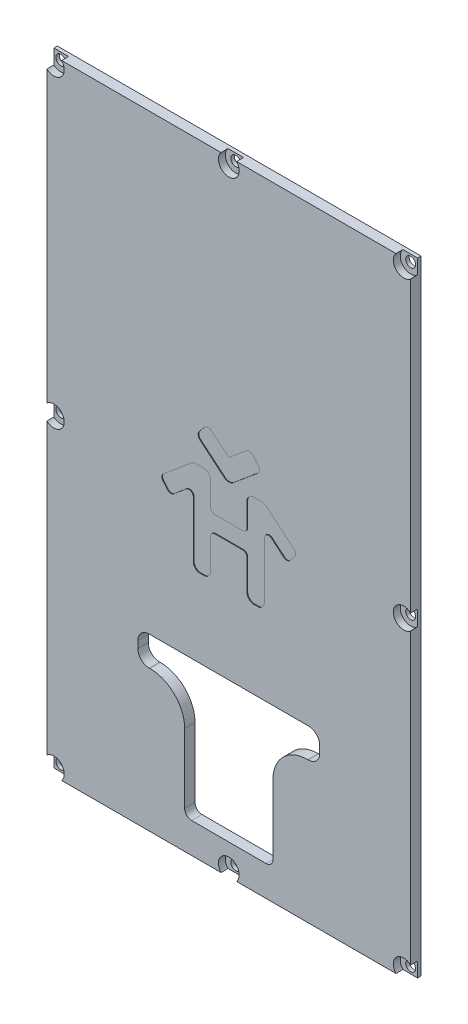
SolidWorks part; units mm, degrees
ref_plane "Спереди" through (0, 0, 0) normal (0, 0, 1) x (1, 0, 0)
ref_plane "Сверху" through (0, 0, 0) normal (0, 1, 0) x (1, 0, 0)
ref_plane "Справа" through (0, 0, 0) normal (1, 0, 0) x (0, 0, -1)
sketch "Эскиз1" plane through (0, 0, 0) normal (0, 0, 1) x (1, 0, 0)
  line L1 (-52.5, -90) -> (52.5, -90)
  line L2 (-52.5, -90) -> (-52.5, 90)
  line L3 (-52.5, 90) -> (52.5, 90)
  line L4 (52.5, -90) -> (52.5, 90)
  line L5 (-52.5, -90) -> (52.5, 90) construction
  line L6 (-52.5, 90) -> (52.5, -90) construction
  point P0 (0, 0)
  dimension "D1" = 105
  dimension "D2" = 180
extrude "Бобышка-Вытянуть1" add sketch "Эскиз1" along normal blind 3
sketch "Эскиз2" plane through (0, 0, 0) normal (0, 0, -1) x (-1, 0, 0)
  line L0 (-26.25, -44) -> (-26.25, -46)
  line L1 (-23, -49.25) -> (-22.75, -49.25)
  line L2 (-12.75, -59.25) -> (-12.75, -79.25)
  line L3 (-10.75, -81.25) -> (10.75, -81.25)
  line L4 (12.75, -79.25) -> (12.75, -59.25)
  line L5 (22.75, -49.25) -> (23, -49.25)
  line L6 (26.25, -46) -> (26.25, -44)
  line L7 (23, -40.75) -> (-23, -40.75)
  line L8 (-52.5, -90) -> (-52.5, 90) construction
  line L9 (52.5, 90) -> (52.5, -90) construction
  line L10 (52.5, -90) -> (-52.5, -90) construction
  arc A0 (22.75, -49.25) -> (12.75, -59.25) centre (22.75, -59.25) ccw
  arc A1 (-12.75, -59.25) -> (-22.75, -49.25) centre (-22.75, -59.25) ccw
  arc A2 (23, -49.25) -> (26.25, -46) centre (23, -46) ccw
  arc A3 (26.25, -44) -> (23, -40.75) centre (23, -44) ccw
  arc A4 (-23, -49.25) -> (-26.25, -46) centre (-23, -46) cw
  arc A5 (-23, -40.75) -> (-26.25, -44) centre (-23, -44) ccw
  arc A6 (12.75, -79.25) -> (10.75, -81.25) centre (10.75, -79.25) cw
  arc A7 (-10.75, -81.25) -> (-12.75, -79.25) centre (-10.75, -79.25) cw
  point P16 (12.75, -49.25)
  point P21 (26.25, -49.25)
  point P24 (26.25, -40.75)
  point P31 (12.75, -81.25)
  point P34 (-12.75, -81.25)
  dimension "D7" = 10
  dimension "D8" = 3.25
  dimension "D9" = 2
  dimension "D1" = 26.25
  dimension "D2" = 26.25
  dimension "D3" = 49.25
  dimension "D4" = 8.5
  dimension "D5" = 25.5
  dimension "D6" = 32
extrude "Вырез-Вытянуть1" cut sketch "Эскиз2" against normal blind 10
sketch "Эскиз3" plane through (0, 0, 3) normal (0, 0, 1) x (1, 0, 0)
  line L0 (-50.5, -940.9285) -> (-50.5, 49059.0715) construction
  line L1 (50.5, -944.6511) -> (50.5, 49055.3489) construction
  line L2 (-1032.3277, 88) -> (48967.6723, 88) construction
  line L3 (-1028.801, -88) -> (48971.199, -88) construction
  line L4 (-52.5, -90) -> (52.5, -90) construction
  line L6 (-52.5, 90) -> (-52.5, -90) construction
  line L7 (52.5, -90) -> (52.5, 90) construction
  line L8 (52.5, 90) -> (-52.5, 90) construction
  line L9 (0, -925) -> (0, 49075) construction
  line L10 (-1052.5, 0) -> (48947.5, 0) construction
  circle A0 centre (-50.5, 88) radius 3
  circle A1 centre (0, 88) radius 3
  circle A2 centre (50.5, 88) radius 3
  circle A3 centre (50.5, 0) radius 3
  circle A4 centre (50.5, -88) radius 3
  circle A5 centre (0, -88) radius 3
  circle A6 centre (-50.5, -88) radius 3
  circle A7 centre (-50.5, 0) radius 3
  point P19 (0, 90)
  point P22 (-52.5, 0)
  dimension "D5" = 6
  dimension "D1" = 2
  dimension "D2" = 2
  dimension "D3" = 2
  dimension "D4" = 2
extrude "Вырез-Вытянуть2" cut sketch "Эскиз3" against normal blind 2
sketch "Эскиз4" plane through (0, 0, 1) normal (0, 0, 1) x (1, 0, 0)
  circle A0 centre (-50.5, 88) radius 1.425
  circle A1 centre (0, 88) radius 1.425
  circle A2 centre (50.5, 88) radius 1.425
  circle A3 centre (50.5, 0) radius 1.425
  circle A4 centre (50.5, -88) radius 1.425
  circle A5 centre (0, -88) radius 1.425
  circle A6 centre (-50.5, -88) radius 1.425
  circle A7 centre (-50.5, 0) radius 1.425
  dimension "D1" = 2.85
extrude "Вырез-Вытянуть3" cut sketch "Эскиз4" against normal blind 2
sketch "Эскиз5" plane through (0, 0, 3) normal (0, 0, 1) x (1, 0, 0)
  line L0 (-10.25, -0.0911) -> (-10.25, -16.2185)
  line L1 (-8.25, -18.2185) -> (-7.25, -18.2185)
  line L2 (-5.25, -16.2185) -> (-5.25, -7.4685)
  line L3 (-4, -6.2185) -> (4, -6.2185)
  line L4 (-9.3401, 8.5815) -> (-7.25, 8.5815)
  line L5 (-5.25, 6.5815) -> (-5.25, -0.1685)
  line L6 (0, -1000.6685) -> (0, 48999.3315) construction
  line L7 (-4, -1.4185) -> (4, -1.4185)
  line L8 (-10.947, 7.9966) -> (-18.868, 1.3501)
  line L9 (-19.0221, -0.4109) -> (-17.6786, -2.012)
  line L10 (-15.9176, -2.1661) -> (-12.3035, 0.8665)
  line L11 (15.9176, -2.1661) -> (12.3035, 0.8665)
  line L12 (19.0221, -0.4109) -> (17.6786, -2.012)
  line L13 (10.947, 7.9966) -> (18.868, 1.3501)
  line L14 (5.25, 6.5815) -> (5.25, -0.1685)
  line L15 (9.3401, 8.5815) -> (7.25, 8.5815)
  line L16 (5.25, -16.2185) -> (5.25, -7.4685)
  line L17 (8.25, -18.2185) -> (7.25, -18.2185)
  line L18 (10.25, -0.0911) -> (10.25, -16.2185)
  line L19 (0, 14.8585) -> (-4.9795, 19.0368)
  line L20 (-7.0927, 18.8519) -> (-8.4839, 17.194)
  line L21 (-8.299, 15.0808) -> (-1.2856, 9.1958)
  line L22 (8.299, 15.0808) -> (1.2856, 9.1958)
  line L23 (0, 14.8585) -> (4.9795, 19.0368)
  line L24 (7.0927, 18.8519) -> (8.4839, 17.194)
  arc A0 (-10.25, -16.2185) -> (-8.25, -18.2185) centre (-8.25, -16.2185) ccw
  arc A1 (-7.25, -18.2185) -> (-5.25, -16.2185) centre (-7.25, -16.2185) ccw
  arc A2 (-5.25, 6.5815) -> (-7.25, 8.5815) centre (-7.25, 6.5815) ccw
  arc A3 (-9.3401, 8.5815) -> (-10.947, 7.9966) centre (-9.3401, 6.0815) ccw
  arc A4 (-4, -6.2185) -> (-5.25, -7.4685) centre (-4, -7.4685) ccw
  arc A5 (-4, -1.4185) -> (-5.25, -0.1685) centre (-4, -0.1685) cw
  arc A6 (-10.25, -0.0911) -> (-12.3035, 0.8665) centre (-11.5, -0.0911) ccw
  arc A7 (-15.9176, -2.1661) -> (-17.6786, -2.012) centre (-16.721, -1.2085) cw
  arc A8 (-18.868, 1.3501) -> (-19.0221, -0.4109) centre (-18.0645, 0.3926) ccw
  arc A9 (18.868, 1.3501) -> (19.0221, -0.4109) centre (18.0645, 0.3926) cw
  arc A10 (15.9176, -2.1661) -> (17.6786, -2.012) centre (16.721, -1.2085) ccw
  arc A11 (10.25, -0.0911) -> (12.3035, 0.8665) centre (11.5, -0.0911) cw
  arc A12 (4, -1.4185) -> (5.25, -0.1685) centre (4, -0.1685) ccw
  arc A13 (4, -6.2185) -> (5.25, -7.4685) centre (4, -7.4685) cw
  arc A14 (9.3401, 8.5815) -> (10.947, 7.9966) centre (9.3401, 6.0815) cw
  arc A15 (5.25, 6.5815) -> (7.25, 8.5815) centre (7.25, 6.5815) cw
  arc A16 (7.25, -18.2185) -> (5.25, -16.2185) centre (7.25, -16.2185) cw
  arc A17 (10.25, -16.2185) -> (8.25, -18.2185) centre (8.25, -16.2185) cw
  arc A18 (-8.299, 15.0808) -> (-8.4839, 17.194) centre (-7.3348, 16.2298) cw
  arc A19 (-4.9795, 19.0368) -> (-7.0927, 18.8519) centre (-5.9437, 17.8877) ccw
  arc A20 (4.9795, 19.0368) -> (7.0927, 18.8519) centre (5.9437, 17.8877) cw
  arc A21 (8.299, 15.0808) -> (8.4839, 17.194) centre (7.3348, 16.2298) ccw
  arc A22 (1.2856, 9.1958) -> (-1.2856, 9.1958) centre (0, 10.7279) cw
  point P35 (0, -6.2185)
  point P36 (0, -1.4185)
  point P61 (19.57, 0.5466)
  point P62 (4.9945, -1.4185)
  point P63 (4.9945, -6.2185)
  point P64 (9.9945, 8.5815)
  point P65 (4.9945, 8.5815)
  point P66 (4.9945, -18.2185)
  point P67 (9.9945, -18.2185)
  point P79 (5.7231, 19.8752)
  point P80 (8.937, 16.0449)
  dimension "D3" = 2
  dimension "D4" = 2.5
  dimension "D6" = 1.5
  dimension "D7" = 2
  dimension "D8" = 1.25
  dimension "D1" = 5.25
  dimension "D2" = 50
  dimension "D5" = 50
extrude "Вырез-Вытянуть4" cut sketch "Эскиз5" against normal blind 0.2
